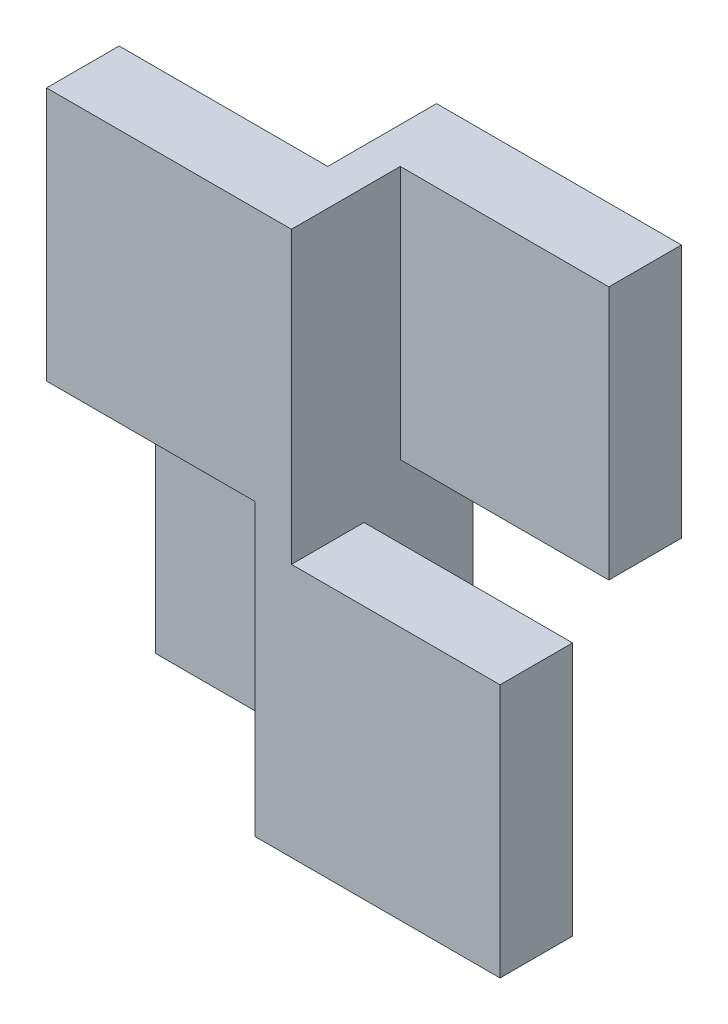
SolidWorks part; units mm, degrees
ref_plane "Front Plane" through (0, 0, 0) normal (0, 0, 1) x (1, 0, 0)
ref_plane "Top Plane" through (0, 0, 0) normal (0, 1, 0) x (1, 0, 0)
ref_plane "Right Plane" through (0, 0, 0) normal (1, 0, 0) x (0, 0, -1)
sketch "Sketch1" plane through (0, 0, 0) normal (0, 0, 1) x (1, 0, 0)
  line L1 (0, 0) -> (0.25, 0)
  line L2 (0, 0) -> (0, 0.3)
  line L3 (0, 0.3) -> (0.25, 0.3)
  line L4 (0.25, 0) -> (0.25, 0.3)
  dimension "D1" = 0.25
  dimension "D2" = 0.3
extrude "Boss-Extrude1" add sketch "Sketch1" along normal blind 0.1 contours L2 L3 L4 L1
sketch "Sketch2" plane through (0, 0, 0) normal (-1, 0, 0) x (0, 0, 1)
  line L0 (0, 0.15) -> (0.1, 0.15) construction
  line L1 (0, 0) -> (0, 0.3) construction
  line L2 (0.1, 0) -> (0.1, 0.3) construction
  line L3 (0.05, 0.3) -> (0.05, 0) construction
  line L4 (0.1, 0.3) -> (0, 0.3) construction
  line L5 (0.1, 0) -> (0, 0) construction
  line L6 (0, 0.16) -> (0.1, 0.16) construction
  line L7 (0.1, 0.14) -> (0, 0.14) construction
  line L8 (0.06, 0.3) -> (0.06, 0) construction
  line L9 (0.04, 0) -> (0.04, 0.3) construction
  line L10 (0, 0.3) -> (0.06, 0.3)
  line L11 (0.06, 0.3) -> (0.06, 0.16)
  line L12 (0.06, 0.16) -> (0.1, 0.16)
  line L13 (0.1, 0.16) -> (0.1, 0)
  line L14 (0.1, 0) -> (0.04, 0)
  line L15 (0.04, 0) -> (0.04, 0.14)
  line L16 (0.04, 0.14) -> (0, 0.14)
  line L17 (0, 0.14) -> (0, 0.3)
  dimension "D1" = 0.01
  dimension "D2" = 0.01
  dimension "D3" = 0.01
  dimension "D4" = 0.01
extrude "Cut-Extrude1" cut sketch "Sketch2" against normal blind 0.115
sketch "Sketch4" plane through (0.25, 0, 0) normal (1, 0, 0) x (0, 0, -1)
  line L0 (-0.05, 0.3) -> (-0.05, 0) construction
  line L1 (-0.1, 0.3) -> (0, 0.3) construction
  line L2 (-0.1, 0) -> (0, 0) construction
  line L3 (-0.1, 0.15) -> (0, 0.15) construction
  line L4 (-0.1, 0) -> (-0.1, 0.3) construction
  line L5 (0, 0) -> (0, 0.3) construction
  line L6 (0, 0.16) -> (-0.1, 0.16) construction
  line L7 (0, 0.14) -> (-0.1, 0.14) construction
  line L8 (-0.06, 0.3) -> (-0.06, 0) construction
  line L9 (-0.04, 0) -> (-0.04, 0.3) construction
  line L10 (-0.1, 0.14) -> (-0.1, 0.3)
  line L11 (-0.1, 0.3) -> (-0.04, 0.3)
  line L12 (-0.04, 0.3) -> (-0.04, 0.16)
  line L13 (-0.04, 0.16) -> (0, 0.16)
  line L14 (0, 0.16) -> (0, 0)
  line L15 (0, 0) -> (-0.06, 0)
  line L16 (-0.06, 0) -> (-0.06, 0.14)
  line L17 (-0.06, 0.14) -> (-0.1, 0.14)
  dimension "D1" = 0.01
  dimension "D2" = 0.01
  dimension "D3" = 0.01
  dimension "D4" = 0.01
extrude "Cut-Extrude2" cut sketch "Sketch4" against normal blind 0.115
equation "\"t\"= 0.25'thickness of the sheets"
equation "\"t_cf\" = 0.115'thickness of single carbon fiber layer"
equation "\"t_kapton\" = 0.025'thickness of single Kapton flex layer"
equation "\"t_fr4\" = 0.1'thickness of FR4 with copper layer"
equation "\"joint_flex\"= 0.1'Width of flextures gap"
equation "\"joint_flex_eff\"= 0.02'Width of flecture after castelation"
equation "\"joint_fold\"= 0.2'Width of folding joints for 90deg fold"
equation "\"gap_tolerance\"= 0.002'Width to have interfecence fit between carbon fiber inserts"
equation "\"assemble_angle\"= 90'Angle of assembly parts"
equation "\"link_lift\"= 0.5'Actuation linkage amplification for the lift motion"
equation "\"link_swing\"= 0.45'Actuation linkage amplification for the swing motion"
equation "\"D1@Sketch1\"=\"t\""
equation "\"D1@Boss-Extrude1\"=\"joint_flex\""
equation "\"D3@Sketch2\"=\"joint_flex_eff\"/2"
equation "\"D4@Sketch2\"=\"joint_flex_eff\"/2"
equation "\"D1@Cut-Extrude1\"=\"t_cf\""
equation "\"D3@Sketch4\"=\"joint_flex_eff\"/2"
equation "\"D4@Sketch4\"=\"joint_flex_eff\"/2"
equation "\"D1@Cut-Extrude2\"=\"t_cf\""
